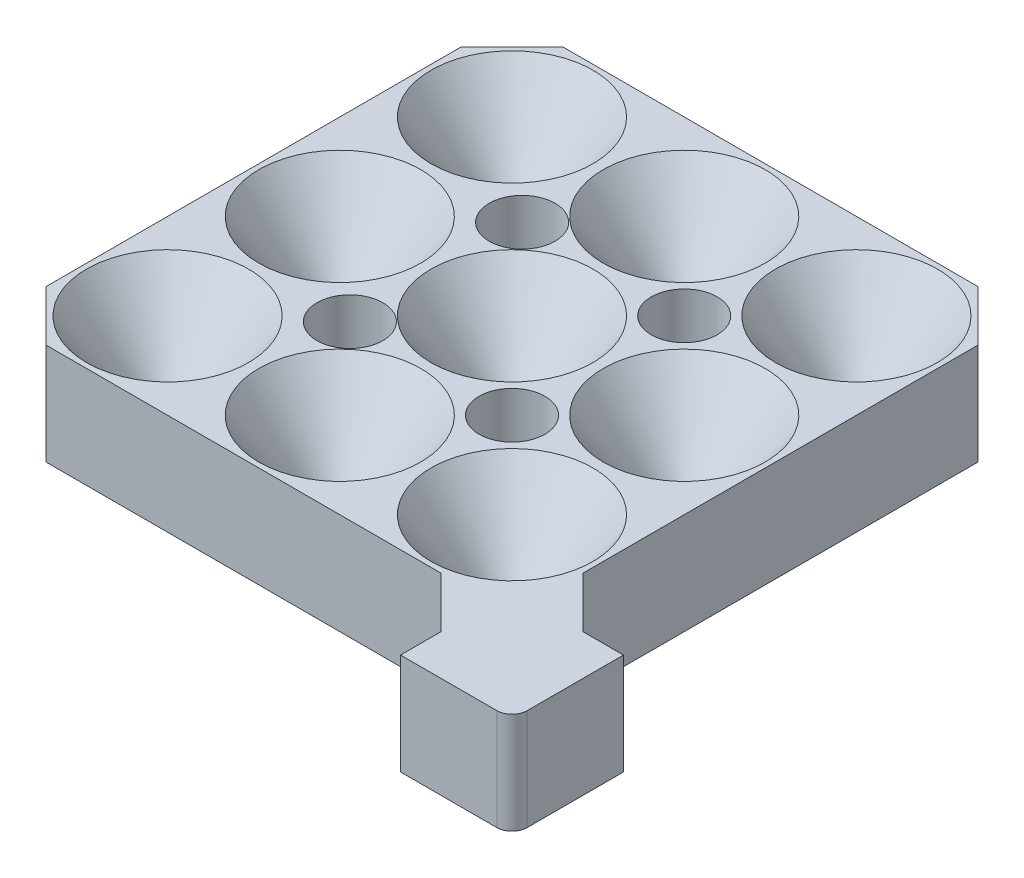
SolidWorks part; units mm, degrees
ref_plane "Piano frontale" through (0, 0, 0) normal (0, 0, 1) x (1, 0, 0)
ref_plane "Piano superiore" through (0, 0, 0) normal (0, 1, 0) x (1, 0, 0)
ref_plane "Piano destro" through (0, 0, 0) normal (1, 0, 0) x (0, 0, -1)
sketch "Schizzo1" plane through (0, 0, 0) normal (0, 1, 0) x (1, 0, 0)
  line L1 (60, -60) -> (-60, -60)
  line L2 (60, -60) -> (60, 60)
  line L3 (60, 60) -> (-60, 60)
  line L4 (-60, -60) -> (-60, 60)
  line L5 (60, -60) -> (-60, 60) construction
  line L6 (60, 60) -> (-60, -60) construction
  point P0 (0, 0)
  dimension "D1" = 120
  dimension "D2" = 120
extrude "Estrusione-Estrusione1" add sketch "Schizzo1" along normal blind 20
ref_plane "Piano1" through (-43, 0, 0) normal (-1, 0, 0) x (0, 0, 1)
ref_plane "Piano2" through (0, 0, -43) normal (0, 0, -1) x (-1, 0, 0)
ref_axis "Assi1" through (-43, 21, -43) along (0, -1, 0)
ref_plane "Piano3" through (0, 5, 0) normal (0, -1, 0) x (-1, 0, 0)
sketch "Schizzo4" plane through (0, 20, 0) normal (0, 1, 0) x (1, 0, 0)
  circle A0 centre (-43, 43) radius 16
  point P3 (0, 0)
  dimension "D1" = 32
sketch "Schizzo5" plane through (0, 5, 0) normal (0, -1, 0) x (-1, 0, 0)
  circle A0 centre (43, 43) radius 5
  dimension "D1" = 10
sketch "Schizzo6" plane through (-43, 0, 0) normal (-1, 0, 0) x (0, 0, 1)
  line L0 (-43, 20) -> (-27, 20)
  line L1 (-27, 20) -> (-59, 20) construction
  line L2 (-60, 20) -> (60, 20) construction
  line L3 (-27, 20) -> (-38, 5)
  line L4 (-66, 5) -> (66, 5) construction
  line L5 (-38, 5) -> (-43, 5)
  line L6 (-48, 5) -> (-38, 5) construction
  line L7 (-43, 5) -> (-43, 20)
  line L8 (-60, 0) -> (60, 0) construction
  dimension "D1" = 16
  dimension "D2" = 5
  dimension "D3" = 5
revolve "Taglia-Rivoluzione4" cut sketch "Schizzo6" angle 360 about L7
extrude "Taglio-Estrusione2" cut sketch "Schizzo5" against normal through all both and the other way through all
pattern_linear "Ripetizione a L1" count 3 spacing 34 along (1, 0, 0) count 3 spacing 34 along (0, 0, 1) of "Taglio-Estrusione2", "Taglia-Rivoluzione4"
sketch "Schizzo7" plane through (0, 20, 0) normal (0, 1, 0) x (1, 0, 0)
  line L0 (-60, -42) -> (38, -42)
  line L1 (-60, 60) -> (-60, -60) construction
  line L2 (38, -42) -> (38, -60)
  line L3 (-60, -60) -> (60, -60) construction
  line L4 (38, -60) -> (60, -60)
  line L5 (60, -60) -> (60, -38)
  line L6 (60, -60) -> (60, 60) construction
  line L7 (60, -38) -> (42, -38)
  line L8 (42, -38) -> (42, 60)
  line L9 (60, 60) -> (-60, 60) construction
  line L10 (60, 60) -> (60, -38)
  line L11 (38, -60) -> (-60, -60)
  line L12 (-60, -60) -> (-60, -42)
  circle A2 centre (25, 43) radius 16 construction
  line M12 (-60, 60) -> (-60, -60)
  line M13 (-60, -60) -> (60, -60)
  line M14 (60, -60) -> (60, 60)
  line M15 (60, 60) -> (-60, 60)
  dimension "D1" = 17
  dimension "D2" = 22
extrude "Taglio-Estrusione3" cut sketch "Schizzo7" against normal blind 20 contours L2 L0 M12 M13 | L8 L7 M14 M15 region at (-11, 20, 51) region at (51, 20, -11)
chamfer "Smusso1" distance 10 angle 45 5 edges at (-60, 10, 42) (-60, 10, -60) (42, 10, -60) (42, 10, 38) (38, 10, 42)
sketch "Schizzo8" plane through (0, 20, 0) normal (0, 1, 0) x (1, 0, 0)
  line L0 (8, 60) -> (8, -42) construction
  line L1 (32, 60) -> (-50, 60) construction
  line L2 (-50, -42) -> (28, -42) construction
  line L3 (-9, 9) -> (-9, -25) construction
  line L4 (25, 9) -> (25, -25) construction
  line L5 (-9, 9) -> (25, 9) construction
  circle A0 centre (8, -8) radius 6.5
  point P13 (8, 9)
  dimension "D2" = 13
  dimension "D1" = 17
extrude "Taglio-Estrusione4" cut sketch "Schizzo8" against normal blind 20
pattern_linear "Ripetizione a L2" count 2 spacing 34 along (0, 0, -1) count 2 spacing 32 along (-1, 0, 0) of "Taglio-Estrusione4"
fillet "Raccordo1" radius 3 1 edges at (60, 10, 60)
